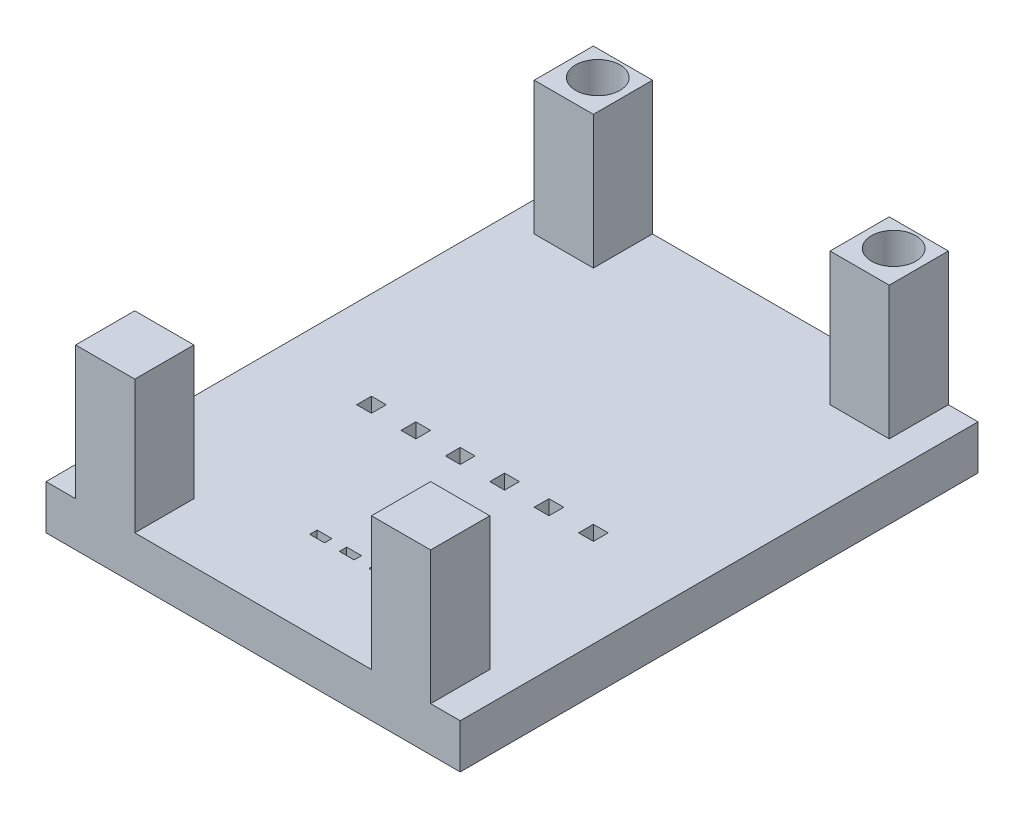
SolidWorks part; units mm, degrees
ref_plane "Plan de face" through (0, 0, 0) normal (0, 0, 1) x (1, 0, 0)
ref_plane "Plan de dessus" through (0, 0, 0) normal (0, 1, 0) x (1, 0, 0)
ref_plane "Plan de droite" through (0, 0, 0) normal (1, 0, 0) x (0, 0, -1)
sketch "Esquisse1" plane through (0, 0, 0) normal (0, 1, 0) x (1, 0, 0)
  line L0 (9, -19) -> (9, -20)
  line L1 (0, 0) -> (28, 0)
  line L2 (0, 0) -> (0, -35)
  line L3 (0, -35) -> (28, -35)
  line L4 (28, 0) -> (28, -35)
  line L5 (6, -19) -> (7, -19)
  line L6 (6, -19) -> (6, -20)
  line L7 (6, -20) -> (7, -20)
  line L8 (7, -19) -> (7, -20)
  line L9 (9, -19) -> (10, -19)
  line L10 (10, -19) -> (10, -20)
  line L11 (9, -20) -> (10, -20)
  line L12 (12, -19) -> (12, -20)
  line L13 (12, -19) -> (13, -19)
  line L14 (13, -19) -> (13, -20)
  line L15 (12, -20) -> (13, -20)
  line L16 (15, -19) -> (15, -20)
  line L17 (15, -19) -> (16, -19)
  line L18 (16, -19) -> (16, -20)
  line L19 (15, -20) -> (16, -20)
  line L20 (18, -19) -> (18, -20)
  line L21 (18, -19) -> (19, -19)
  line L22 (19, -19) -> (19, -20)
  line L23 (18, -20) -> (19, -20)
  line L24 (21, -19) -> (21, -20)
  line L25 (21, -19) -> (22, -19)
  line L26 (22, -19) -> (22, -20)
  line L27 (21, -20) -> (22, -20)
  line L28 (14, -28.6724) -> (14, -29.1724)
  line L29 (12, -28.6724) -> (13, -28.6724)
  line L30 (12, -28.6724) -> (12, -29.1724)
  line L31 (12, -29.1724) -> (13, -29.1724)
  line L32 (13, -28.6724) -> (13, -29.1724)
  line L33 (14, -28.6724) -> (15, -28.6724)
  line L34 (15, -28.6724) -> (15, -29.1724)
  line L35 (14, -29.1724) -> (15, -29.1724)
  line L36 (16, -28.6724) -> (16, -29.1724)
  line L37 (16, -28.6724) -> (17, -28.6724)
  line L38 (17, -28.6724) -> (17, -29.1724)
  line L39 (16, -29.1724) -> (17, -29.1724)
  line L40 (2, -4) -> (2, -31) construction
  line L41 (22, -4) -> (26, -4)
  line L42 (22, -4) -> (22, 0)
  line L43 (22, 0) -> (26, 0)
  line L44 (26, -4) -> (26, 0)
  line L45 (2, -4) -> (6, -4)
  line L46 (2, -4) -> (2, 0)
  line L47 (2, 0) -> (6, 0)
  line L48 (6, -4) -> (6, 0)
  line L49 (2, -31) -> (6, -31)
  line L50 (2, -31) -> (2, -35)
  line L51 (2, -35) -> (6, -35)
  line L52 (6, -31) -> (6, -35)
  line L53 (26, -35) -> (22, -35)
  line L54 (26, -35) -> (26, -31)
  line L55 (26, -31) -> (22, -31)
  line L56 (22, -35) -> (22, -31)
  line L57 (6, -4) -> (6, -31) construction
  line L58 (22, -4) -> (22, -34.5396) construction
  circle A0 centre (4, -1.7) radius 1.5
  circle A1 centre (24, -1.7) radius 1.5
  point P10 (9, -19.5)
  dimension "D9" = 3
  dimension "D10" = 3
  dimension "D13" = 1.7
  dimension "D14" = 1.7
  dimension "D1" = 35
  dimension "D2" = 28
  dimension "D3" = 1
  dimension "D4" = 1
  dimension "D6" = 19
  dimension "D7" = 6
  dimension "D8" = 2
  dimension "D11" = 4
  dimension "D12" = 4
  dimension "D15" = 1
  dimension "D16" = 0.5
  dimension "D18" = 12
  dimension "D19" = 4
  dimension "D20" = 4
  dimension "D21" = 2
  dimension "D22" = 4
  dimension "D23" = 4
  dimension "D24" = 2
  dimension "D25" = 4
  dimension "D26" = 4
  dimension "D27" = 4
  dimension "D28" = 4
  dimension "D5" = 6
  dimension "D17" = 3
extrude "Boss.-Extru.2" add sketch "Esquisse1" along normal blind 3 contours L3 L56 L55 L54 L4 L1 L44 L41 L42 L48 L45 L46 L2 L50 L49 L52 L39 L36 L37 L38 L35 L28 L33 L34 L27 L24 L25 L26 L23 L20 L21 L22 L19 L16 L17 L18 L15 L12 L13 L14 region at (13.9992, 0, 17.4679)
extrude "Boss.-Extru.3" add sketch "Esquisse1<4>" along normal blind 12 contours L56 L3 L54 L55 | L52 L49 L50 L3 | A1 | A0 | L46 L47 L48 L45 | L42 L43 L44 L41 region at (4, 0, 33) region at (24, 0, 33) region at (4, 0, 1.7) region at (24, 0, 1.7)
sketch "Esquisse1<4>" plane through (0, 0, 0) normal (0, 1, 0) x (1, 0, 0) same geometry as "Esquisse1"
